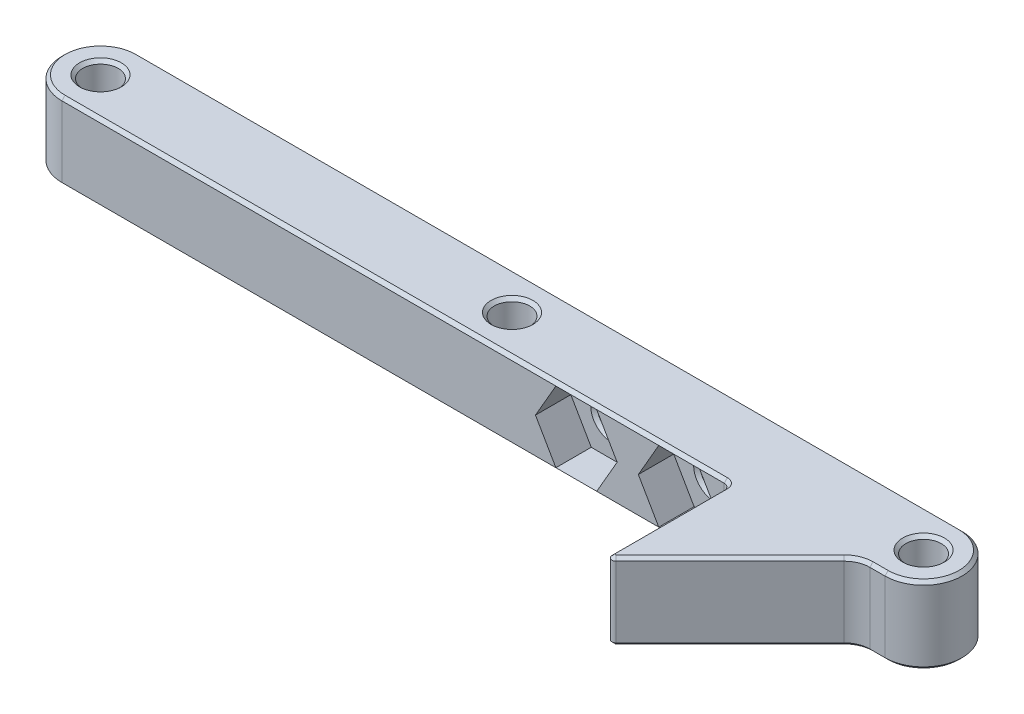
SolidWorks part; units mm, degrees
ref_plane "Front Plane" through (0, 0, 0) normal (0, 0, 1) x (1, 0, 0)
ref_plane "Top Plane" through (0, 0, 0) normal (0, 1, 0) x (1, 0, 0)
ref_plane "Right Plane" through (0, 0, 0) normal (1, 0, 0) x (0, 0, -1)
sketch "Sketch1" plane through (0, 0, 0) normal (0, 1, 0) x (1, 0, 0)
  line L0 (0, 0) -> (-101.6, 0) construction
  line L1 (0, -4.7625) -> (-1.8599, -4.7625)
  line L2 (0, 4.7625) -> (-101.6, 4.7625)
  line L3 (-19.05, -5.5563) -> (-19.05, -19.4111)
  line L4 (-18.1828, -19.7703) -> (-4.1049, -5.6924)
  line L5 (-19.8438, -4.7625) -> (-101.6, -4.7625)
  circle A0 centre (0, 0) radius 2.1828
  circle A1 centre (-50.8, 0) radius 2.1828
  circle A2 centre (-101.6, 0) radius 2.1828
  arc A3 (0, -4.7625) -> (0, 4.7625) centre (0, 0) ccw
  arc A4 (-101.6, 4.7625) -> (-101.6, -4.7625) centre (-101.6, 0) ccw
  arc A5 (-19.05, -5.5563) -> (-19.8438, -4.7625) centre (-19.8438, -5.5563) ccw
  arc A6 (-4.1049, -5.6924) -> (-1.8599, -4.7625) centre (-1.8599, -7.9375) cw
  arc A7 (-19.05, -19.4111) -> (-18.1828, -19.7703) centre (-18.542, -19.4111) ccw
  point P7 (-50.8, 0)
  point P12 (-17.2746, -13.4497)
  point P18 (-19.05, -4.7625)
  point P21 (-3.175, -4.7625)
  point P24 (-19.05, -20.6375)
  dimension "D1" = 4.3656
  dimension "D2" = 4.3656
  dimension "D3" = 4.3656
  dimension "D6" = 4.7625
  dimension "D10" = 0.7937
  dimension "D11" = 3.175
  dimension "D12" = 0.508
  dimension "D4" = 50.8
  dimension "D5" = 50.8
  dimension "D7" = 19.05
  dimension "D8" = 15.875
  dimension "D9" = 15.875
extrude "Boss-Extrude1" add sketch "Sketch1" along normal blind 9.525
sketch "Sketch5" plane through (0, 0, 4.7625) normal (0, 0, 1) x (1, 0, 0)
  line L0 (-101.6, 0) -> (-19.8438, 0) construction
  line L1 (-20.359, 4.7625) -> (-22.8795, 9.1281)
  line L2 (-22.8795, 9.1281) -> (-27.9205, 9.1281)
  line L3 (-27.9205, 9.1281) -> (-30.441, 4.7625)
  line L4 (-30.441, 4.7625) -> (-27.9205, 0.3969)
  line L5 (-27.9205, 0.3969) -> (-22.8795, 0.3969)
  line L6 (-22.8795, 0.3969) -> (-20.359, 4.7625)
  line L7 (-33.059, 4.7625) -> (-35.5795, 9.1281)
  line L8 (-35.5795, 9.1281) -> (-40.6205, 9.1281)
  line L9 (-40.6205, 9.1281) -> (-43.141, 4.7625)
  line L10 (-43.141, 4.7625) -> (-40.6205, 0.3969)
  line L11 (-40.6205, 0.3969) -> (-35.5795, 0.3969)
  line L12 (-35.5795, 0.3969) -> (-33.059, 4.7625)
  circle A0 centre (-25.4, 4.7625) radius 4.3656 construction
  circle A1 centre (-38.1, 4.7625) radius 4.3656 construction
  point P9 (-25.4, 5.1292)
  point P20 (0, 0)
  dimension "D1" = 25.4
  dimension "D2" = 12.7
  dimension "D3" = 8.7312
  dimension "D4" = 4.7625
extrude "Cut-Extrude2" cut sketch "Sketch5" against normal blind 4.3656
sketch "Sketch6" plane through (0, 0, 0.3969) normal (0, 0, 1) x (1, 0, 0)
  line L0 (-101.6, 0) -> (-19.8438, 0) construction
  circle A0 centre (-38.1, 4.7625) radius 2.1828
  circle A1 centre (-25.4, 4.7625) radius 2.1828
  point P7 (0, 0)
  dimension "D4" = 4.3656
  dimension "D5" = 4.3656
  dimension "D1" = 25.4
  dimension "D2" = 12.7
  dimension "D3" = 4.7625
extrude "Cut-Extrude3" cut sketch "Sketch6" against normal through all both and the other way through all
chamfer "Chamfer1" distance 0.3969 angle 45 30 edges at (-101.6, 9.525, 2.1828) (0, 9.525, 2.1828) (-0.9299, 9.525, 4.7625) (-3.0749, 9.525, 5.0042) (-11.1439, 9.525, 12.7314) (-18.7364, 9.525, 19.8804) (-19.05, 9.525, 12.4837) (-19.2825, 9.525, 4.995) (-60.7219, 9.525, 4.7625) (-106.3625, 9.525, 0) (-50.8, 9.525, -4.7625) (4.7625, 9.525, 0) (-50.8, 9.525, 2.1828) (-101.6, 0, 2.1828) (-50.8, 0, 2.1828) (0, 0, 2.1828) (-50.8, 0, -4.7625) (-106.3625, 0, 0) (-60.7219, 0, 4.7625) (-19.2825, 0, 4.995) (-19.05, 0, 12.4837) (-18.7364, 0, 19.8804) (-11.1439, 0, 12.7314) (-3.0749, 0, 5.0042) (-0.9299, 0, 4.7625) (4.7625, 0, 0) (-23.2172, 4.7625, -4.7625) (-23.2172, 4.7625, 0.3969) (-35.9172, 4.7625, -4.7625) (-35.9172, 4.7625, 0.3969)
